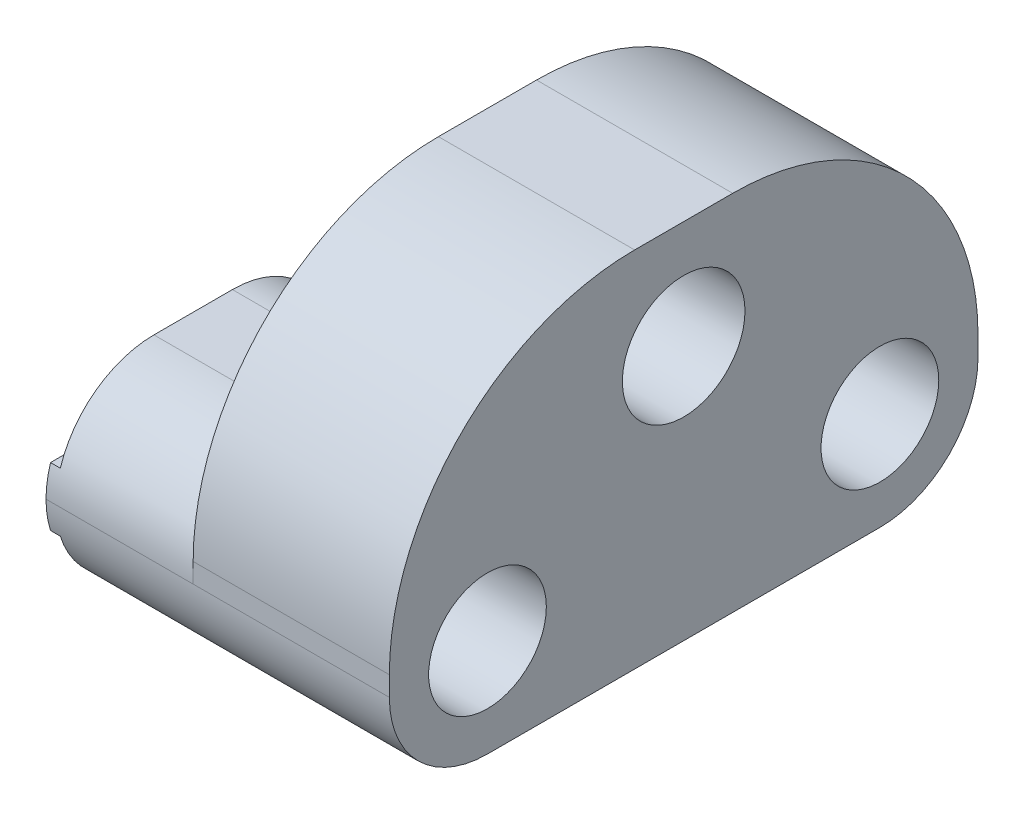
SolidWorks part; units mm, degrees
ref_plane "Alzado" through (0, 0, 0) normal (0, 0, 1) x (1, 0, 0)
ref_plane "Planta" through (0, 0, 0) normal (0, 1, 0) x (1, 0, 0)
ref_plane "Vista lateral" through (0, 0, 0) normal (1, 0, 0) x (0, 0, -1)
sketch "Croquis1" plane through (0, 0, 0) normal (0, 0, 1) x (1, 0, 0)
  line L9 (0, 0) -> (0, 7)
  line L10 (0, 7) -> (-1, 7)
  line L11 (-1, 7) -> (-1, 13)
  line L12 (-1, 13) -> (0, 13)
  line L13 (0, 13) -> (0, 20)
  line L14 (0, 20) -> (14, 20)
  line L15 (14, 20) -> (14, 37)
  line L16 (14, 37) -> (34, 37)
  line L17 (34, 37) -> (34, 0)
  line L18 (34, 0) -> (0, 0)
  point P3 (-1, 10)
  dimension "D1" = 6
  dimension "D2" = 20
  dimension "D3" = 14
  dimension "D4" = 20
  dimension "D5" = 1
  dimension "D6" = 10
  dimension "D7" = 17
extrude "Saliente-Extruir1" add sketch "Croquis1" along normal blind 60
sketch "Croquis2" plane through (34, 0, 0) normal (1, 0, 0) x (0, 0, -1)
  line L0 (-60, 0) -> (-60, 37) construction
  line L1 (0, 0) -> (0, 37) construction
  line L3 (-60, 0) -> (0, 0) construction
  circle A0 centre (-50, 10) radius 2.75
  circle A1 centre (-10, 10) radius 2.75
  dimension "D1" = 5.5
  dimension "D2" = 5.5
  dimension "D3" = 10
  dimension "D4" = 10
  dimension "D5" = 10
  dimension "D6" = 10
extrude "Cortar-Extruir1" cut sketch "Croquis2" against normal up to surface (35 mm away) up to face at (-1, 10, 30)
sketch "Croquis3" plane through (34, 0, 0) normal (1, 0, 0) x (0, 0, -1)
  circle A0 centre (-50, 10) radius 6
  circle A1 centre (-10, 10) radius 6
  dimension "D1" = 12
  dimension "D2" = 12
extrude "Cortar-Extruir2" cut sketch "Croquis3" against normal blind 28
sketch "Croquis4" plane through (34, 0, 0) normal (1, 0, 0) x (0, 0, -1)
  line L0 (-60, 37) -> (0, 37) construction
  circle A0 centre (-30, 26) radius 6.25
  point P4 (-30, 37)
  dimension "D1" = 12.5
  dimension "D2" = 0
  dimension "D3" = 6
extrude "Cortar-Extruir3" cut sketch "Croquis4" against normal up to next
sketch "Croquis5" plane through (14, 0, 0) normal (-1, 0, 0) x (0, 0, 1)
  circle A0 centre (30, 26) radius 10
  dimension "D1" = 20
extrude "Cortar-Extruir4" cut sketch "Croquis5" along normal up to surface (14 mm away) up to face at (0, 17.625, 30)
fillet "Redondeo1" radius 10 2 edges at (7, 20, 22) (7, 20, 38)
fillet "Redondeo2" radius 10 4 edges at (17, 0, 60) (7, 20, 60) (17, 0, 0) (7, 20, 0)
fillet "Redondeo5" radius 25 2 edges at (24, 37, 60) (24, 37, 0)
